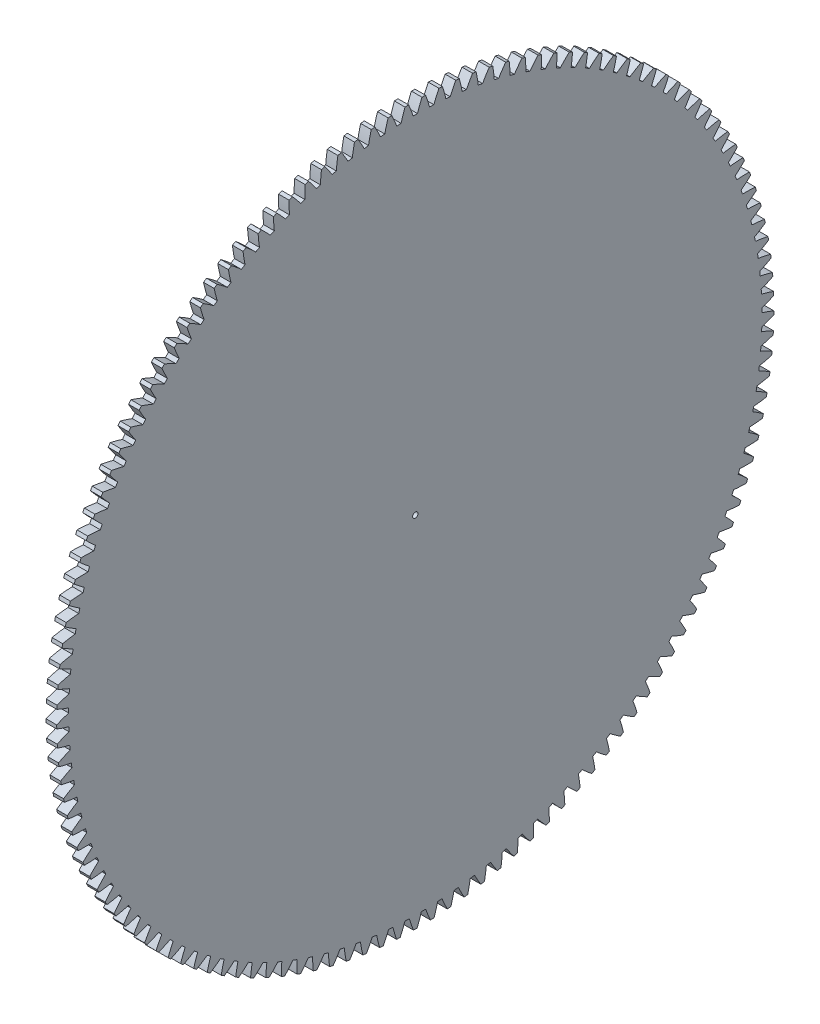
SolidWorks part; units mm, degrees
ref_plane "Plane1" through (0, 0, 0) normal (0, 0, 1) x (1, 0, 0)
ref_plane "Plane2" through (0, 0, 0) normal (0, 1, 0) x (1, 0, 0)
ref_plane "Plane3" through (0, 0, 0) normal (1, 0, 0) x (0, 0, -1)
sketch "HoldingSke" plane through (0, 0, 0) normal (0, 1, 0) x (1, 0, 0)
  line L0 (0, 0) -> (-0.682, -0.7314)
  line L1 (-15, 0) -> (100, 0) construction
  line L2 (0, 0) -> (-2.1039, 2.3779)
  line L3 (0, 0) -> (-11.863, 4.5341)
  line L4 (0, 0) -> (-5.8897, 6.316)
  line L5 (0, 0) -> (-46.8476, -17.4728)
  line L6 (0, 0) -> (-1.6579, -1.1186)
  line L7 (-2.1039, 2.3779) -> (8.6586, 51.2059)
  line L8 (-76.2, 54.61) -> (-76.1, 54.61)
  line L9 (-71.009, 38.7566) -> (-53.1078, 45.2721)
  line L10 (-76.2, 71.12) -> (104.1128, 71.12)
  line L11 (0, 0) -> (-2, 0)
  line L12 (-76.2, 101.6) -> (-76.162, 101.6)
  line L13 (24.9733, 27.94) -> (52.9518, 28.4284)
  line L14 (24.9733, 27.94) -> (24.9743, 27.94)
  line L15 (24.9733, 27.94) -> (100.4006, 29.5858)
  line L16 (-63.627, -1) -> (-12.827, -1)
  circle A0 centre (0, 0) radius 0.5
  circle A1 centre (0, 0) radius 37.5
  circle A2 centre (0, 0) radius 37.5
  circle A3 centre (0, 0) radius 0.5
  dimension "Num_teeth" = 133
  dimension "Pitch_radius" = 180.3128
  dimension "Width" = 2
  dimension "Thickness" = 2
sketch "BasProSke" plane through (0, 0, 0) normal (0, 1, 0) x (1, 0, 0)
  line L0 (-10, 0) -> (60, 0) construction
  line L1 (0, 0) -> (0, 67.5)
  line L2 (0, 0) -> (2, 0)
  line L3 (2, 0) -> (2, 67.5)
  line L4 (2, 67.5) -> (0, 67.5)
  dimension "Thickness" = 2
  dimension "Diameter" = 135
revolve "Base-Revolve" add sketch "BasProSke" angle 360 about L0
sketch "TooCutSke" plane through (0, 0, 0) normal (1, 0, 0) x (0, 0, -1)
  line L1 (0, 0) -> (0, 107) construction
  line L2 (0, 0) -> (-0.8519, 66.4945) construction
  line L3 (0, 0) -> (-3.1411, 132.9551) construction
  line L4 (-0.8519, 66.4945) -> (-1.5706, 66.4776) construction
  arc A0 (0.4088, 65.2477) -> (-0.4088, 65.2477) centre (0, 0) ccw
  arc A1 (1.2672, 67.5135) -> (-1.2672, 67.5135) centre (0, 0) ccw
  circle A2 centre (0, 0) radius 66.5 construction
  circle A3 centre (0, 0) radius 62.4896 construction
  arc A4 (-0.4088, 65.2477) -> (-1.2672, 67.5135) centre (-25.6867, 56.9661) ccw
  arc A5 (1.2672, 67.5135) -> (0.4088, 65.2477) centre (25.6867, 56.9661) ccw
extrude "ToothCut" cut sketch "TooCutSke" along normal through all
fillet "Breaks" [suppressed] radius 0.02 tangent propagation no
fillet "RootFillets" [suppressed] radius 0.251
pattern_circular "TeethCuts" count 133 every 2.707 about axis through (-10, 0, 0) along (1, 0, 0) of "ToothCut", "RootFillets", "Breaks"
sketch "HubNeaOneSke" plane through (0, 0, 0) normal (-1, 0, 0) x (0, 0, 1)
  circle A0 centre (0, 0) radius 37.5
  dimension "Diameter" = 75
extrude "HubNearOne" [suppressed] add sketch "HubNeaOneSke" along normal blind 48.0001
sketch "HubNeaBotSke" plane through (0, 0, 0) normal (-1, 0, 0) x (0, 0, 1)
  circle A0 centre (0, 0) radius 37.5
  dimension "Diameter" = 75
extrude "HubNearBoth" [suppressed] add sketch "HubNeaBotSke" along normal blind 24
ref_plane "FarPln" through (2, 0, 0) normal (1, 0, 0) x (0, 0, -1)
sketch "HubFarSke" plane through (2, 0, 0) normal (1, 0, 0) x (0, 0, -1)
  circle A0 centre (0, 0) radius 37.5
  dimension "Diameter" = 75
extrude "HubFar" [suppressed] add sketch "HubFarSke" along normal blind 24
sketch "BorSke" plane through (0, 0, 0) normal (1, 0, 0) x (0, 0, -1)
  circle A0 centre (0, 0) radius 0.5
  dimension "Diameter" = 1
extrude "Bore" cut sketch "BorSke" along normal mid plane 100.0001
sketch "KeySke" plane through (0, 0, 0) normal (1, 0, 0) x (0, 0, -1)
  line L0 (-0.05, 0) -> (-0.05, 0.6)
  line L1 (-0.05, 0.6) -> (0.05, 0.6)
  line L2 (0.05, 0.6) -> (0.05, 0)
  line L3 (0, 0) -> (0, 34) construction
  line L4 (-0.05, 0) -> (0.05, 0)
extrude "Keyway" [suppressed] cut sketch "KeySke" along normal mid plane 100.0001
pattern_circular "Keyway2" [suppressed] count 2 every 90 about axis through (-10, 0, 0) along (1, 0, 0) reverse direction yes
equation "' \"Module@HoldingSke\" = 6.35"
equation "' \"Num_teeth@HoldingSke\" = 12"
equation "' \"Ap@HoldingSke\" =  20"
equation "' \"Ap@HoldingSke\" = 20"
equation "' \"Width@HoldingSke\" = 0.5 * 25.4"
equation "' \"Hub_dia@HoldingSke\"= 1 * 25.4"
equation "' \"Hub_dia@HoldingSke\" = 1 * 25.4"
equation "' \"Overall_len@HoldingSke\" = 1.0 * 25.4"
equation "' \"Bore@HoldingSke\" = 0.75 * 25.4"
equation "' \"T_dim@HoldingSke\" = 0.1 * 25.4"
equation "' \"Width@KeySke\" = 0.25 * 25.4"
equation "' \"Show_teeth@HoldingSke\" = 13"
equation "' \"Backlash@HoldingSke\" = 0.009 * 25.4"
equation "' \"Addendum_fac@HoldingSke\" = 1.0"
equation "' \"Dedendum_fac@HoldingSke\" = 1.25"
equation "' \"Dedendum_add@HoldingSke\" = 0.00005 * 25.4"
equation "' \"Clearance_fac@HoldingSke\" = 0.25"
equation "\"Pitch@HoldingSke\" = 1 / \"Module@HoldingSke\""
equation "\"Overcut_dia@TooCutSke\" = (\"Num_teeth@HoldingSke\" + 2 * \"Addendum_fac@HoldingSke\") / \"Pitch@HoldingSke\" + 0.002 * 25.4"
equation "\"Pitch_dia@TooCutSke\" = \"Num_teeth@HoldingSke\" / \"Pitch@HoldingSke\""
equation "\"Base_dia@TooCutSke\" = \"Num_teeth@HoldingSke\" / \"Pitch@HoldingSke\" * cos((\"Ap@HoldingSke\"  * 3.14159265 / 180))"
equation "\"Root_dia@TooCutSke\" = (\"Num_teeth@HoldingSke\" + 2) / \"Pitch@HoldingSke\" - 2 * (\"Addendum_fac@HoldingSke\" + \"Dedendum_fac@HoldingSke\") / \"Pitch@HoldingSke\" - \"Dedendum_add@HoldingSke\" * 2"
equation "\"Half_ang@TooCutSke\" = 180 / \"Num_teeth@HoldingSke\""
equation "\"Half_CT@TooCutSke\" = \"Num_teeth@HoldingSke\" / \"Pitch@HoldingSke\" * sin((3.14159265 / 2 / \"Num_teeth@HoldingSke\")) / 2 - 7 * \"Backlash@HoldingSke\" / 4"
equation "\"Flank_rad@TooCutSke\" = \"Num_teeth@HoldingSke\" / \"Pitch@HoldingSke\" / 5"
equation "\"Radius@RootFillets\" = \"Clearance_fac@HoldingSke\" / \"Pitch@HoldingSke\" + \"Dedendum_add@HoldingSke\""
equation "\"Break_rad@Breaks\" = 0.02 / \"Pitch@HoldingSke\""
equation "\"Thickness@HoldingSke\" = \"Width@HoldingSke\""
equation "\"OAL@HoldingSke\" = \"Thickness@HoldingSke\""
equation "\"MHD@HoldingSke\" = (\"Num_teeth@HoldingSke\" + 2) / \"Pitch@HoldingSke\" - 2 * (\"Addendum_fac@HoldingSke\" + \"Dedendum_fac@HoldingSke\")  / \"Pitch@HoldingSke\" - \"Dedendum_add@HoldingSke\" * 2"
equation "\"MBD@HoldingSke\" = (\"Num_teeth@HoldingSke\" + 2) / \"Pitch@HoldingSke\" - 2 * (\"Addendum_fac@HoldingSke\" + \"Dedendum_fac@HoldingSke\")  / \"Pitch@HoldingSke\" - \"Dedendum_add@HoldingSke\" * 2 - 0.002 * 25.4"
equation "\"MHD@HoldingSke\" = ((sgn( \"MHD@HoldingSke\" - \"Hub_dia@HoldingSke\" )-1)*( \"MHD@HoldingSke\" - \"Hub_dia@HoldingSke\" ))/-2+ \"Hub_dia@HoldingSke\""
equation "\"MBD@HoldingSke\" = ((sgn( \"MBD@HoldingSke\" - \"Bore@HoldingSke\" )-1)*( \"MBD@HoldingSke\" - \"Bore@HoldingSke\" ))/-2+ \"Bore@HoldingSke\""
equation "\"OAL@HoldingSke\" = ((sgn( \"OAL@HoldingSke\" - \"Overall_len@HoldingSke\" )+1)*( \"OAL@HoldingSke\" - \"Overall_len@HoldingSke\" ))/2 + \"Overall_len@HoldingSke\" + 0.000002 * 25.4"
equation "\"Num_teeth@TeethCuts\" = int( \"Show_teeth@HoldingSke\" ) + 1"
equation "\"Num_teeth@TeethCuts\" = ((sgn( \"Num_teeth@TeethCuts\" - \"Num_teeth@HoldingSke\" )-1)*( \"Num_teeth@TeethCuts\" - \"Num_teeth@HoldingSke\" ))/-2+ \"Num_teeth@HoldingSke\""
equation "\"Num_teeth@TeethCuts\" = ((sgn( \"Num_teeth@TeethCuts\" - 2.0)+1)*( \"Num_teeth@TeethCuts\" - 2.0))/2 +2.0"
equation "\"Angle@TeethCuts\" = 360.0 / \"Num_teeth@HoldingSke\""
equation "\"Diameter@BasProSke\" = (\"Num_teeth@HoldingSke\" + 2 * \"Addendum_fac@HoldingSke\") / \"Pitch@HoldingSke\""
equation "\"Thickness@BasProSke\"  = \"Thickness@HoldingSke\""
equation "' \"Fillet_rad@BasProSke\" =  \"Thickness@HoldingSke\" * 0.05"
equation "' \"Fillet_rad@BasProSke\" = \"Thickness@HoldingSke\" * 0.05"
equation "\"MHD@HoldingSke\" = ((sgn( \"MHD@HoldingSke\" - \"Root_dia@TooCutSke\" )-1)*( \"MHD@HoldingSke\" - \"Root_dia@TooCutSke\" ))/-2+ \"Root_dia@TooCutSke\""
equation "\"Diameter@HubNeaOneSke\" = \"MHD@HoldingSke\""
equation "\"Length@HubNearOne\" = \"OAL@HoldingSke\" - \"Thickness@BasProSke\""
equation "\"Diameter@HubNeaBotSke\" = \"MHD@HoldingSke\""
equation "\"Length@HubNearBoth\" = ( \"OAL@HoldingSke\" - \"Thickness@BasProSke\" ) / 2.0"
equation "\"Thickness@FarPln\" = \"Thickness@BasProSke\""
equation "\"Diameter@HubFarSke\" = \"MHD@HoldingSke\""
equation "\"Length@HubFar\" = ( \"OAL@HoldingSke\" - \"Thickness@BasProSke\" ) / 2.0"
equation "\"Diameter@BorSke\" = \"MBD@HoldingSke\""
equation "\"D1@Bore\" = \"OAL@HoldingSke\" * 2.0"
equation "\"D1@Keyway\" = \"OAL@HoldingSke\" * 2.0"
equation "\"Offset@KeySke\" = \"T_dim@HoldingSke\" + \"MBD@HoldingSke\" / 2.0"
